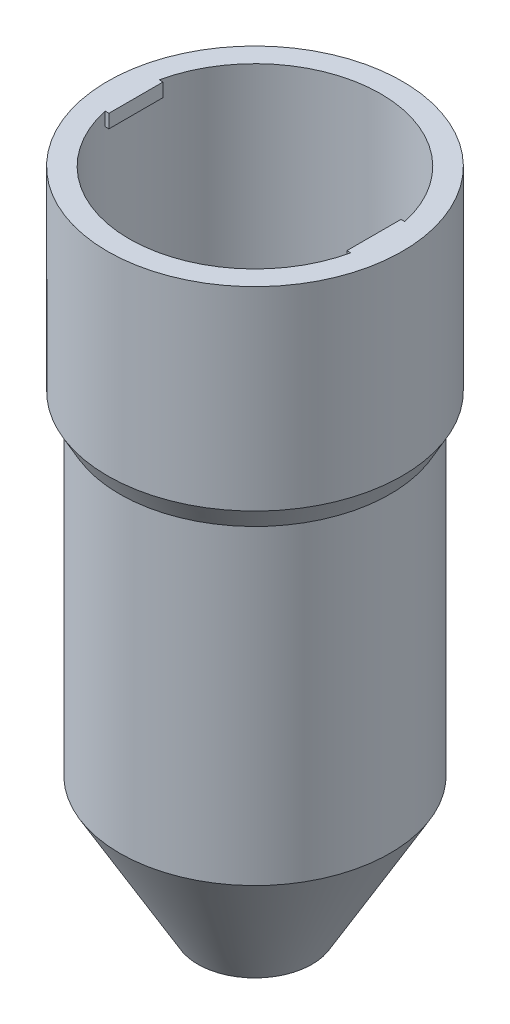
SolidWorks part; units mm, degrees
ref_plane "Front Plane" through (0, 0, 0) normal (0, 0, 1) x (1, 0, 0)
ref_plane "Top Plane" through (0, 0, 0) normal (0, 1, 0) x (1, 0, 0)
ref_plane "Right Plane" through (0, 0, 0) normal (1, 0, 0) x (0, 0, -1)
sketch "Sketch1" plane through (0, 0, 0) normal (0, 1, 0) x (1, 0, 0)
  circle A0 centre (0, 0) radius 2.75
  circle A1 centre (0, 0) radius 5
  dimension "D1" = 5.5
  dimension "D2" = 2.25
extrude "Boss-Extrude1" add sketch "Sketch1" along normal blind 16
sketch "Sketch2" plane through (0, 0, 0) normal (0, -1, 0) x (1, 0, 0)
  circle A0 centre (0, 0) radius 5
  circle A1 centre (0, 0) radius 5 construction
  dimension "D1" = 0
extrude "Boss-Extrude2" add sketch "Sketch2" along normal blind 1.5
sketch "Sketch3" plane through (0, 0, 0) normal (0, 1, 0) x (1, 0, 0)
  circle A0 centre (0, 0) radius 0.75
  dimension "D1" = 1.5
extrude "Cut-Extrude1" cut sketch "Sketch3" against normal blind 1.5
chamfer "Chamfer1" distance 5 angle 30 1 edges at (0, -1.5, -5) first distance on face at (0, 16, 5)
chamfer "Chamfer2" distance 2 angle 30 1 edges at (0, 0, 2.75) first distance on face at (0, 16, 2.75)
fillet "Fillet1" radius 1 1 edges at (0, 16, 2.75)
sketch "Sketch5" plane through (0, 16, 0) normal (0, 1, 0) x (1, 0, 0)
  circle A0 centre (0, 0) radius 4.65
  circle A1 centre (0, 0) radius 5.45
  dimension "D1" = 9.3
  dimension "D2" = 0.8
extrude "Boss-Extrude4" add sketch "Sketch5" along normal blind 7
chamfer "Chamfer4" distance 1 angle 29 1 edges at (0, 16, 5) first distance on face at (0, 3.5, -5)
sketch "Sketch6" plane through (0, 23, 0) normal (0, 1, 0) x (1, 0, 0)
  line L1 (4.4, 1) -> (4.9, 1)
  line L2 (4.4, 1) -> (4.4, -1)
  line L3 (4.4, -1) -> (4.9, -1)
  line L4 (4.9, 1) -> (4.9, -1)
  line L5 (4.4, 1) -> (4.9, -1) construction
  line L6 (4.4, -1) -> (4.9, 1) construction
  line L7 (-4.9, 1) -> (-4.4, 1)
  line L8 (-4.9, 1) -> (-4.9, -1)
  line L9 (-4.9, -1) -> (-4.4, -1)
  line L10 (-4.4, 1) -> (-4.4, -1)
  line L11 (-4.9, 1) -> (-4.4, -1) construction
  line L12 (-4.9, -1) -> (-4.4, 1) construction
  circle A0 centre (0, 0) radius 4.65 construction
  circle A1 centre (0, 0) radius 4.65 construction
  point P0 (4.65, 0)
  point P7 (-4.65, 0)
  dimension "D1" = 2
  dimension "D2" = 0.5
  dimension "D3" = 2
  dimension "D4" = 0.5
extrude "Boss-Extrude5" add sketch "Sketch6" against normal blind 0.5
